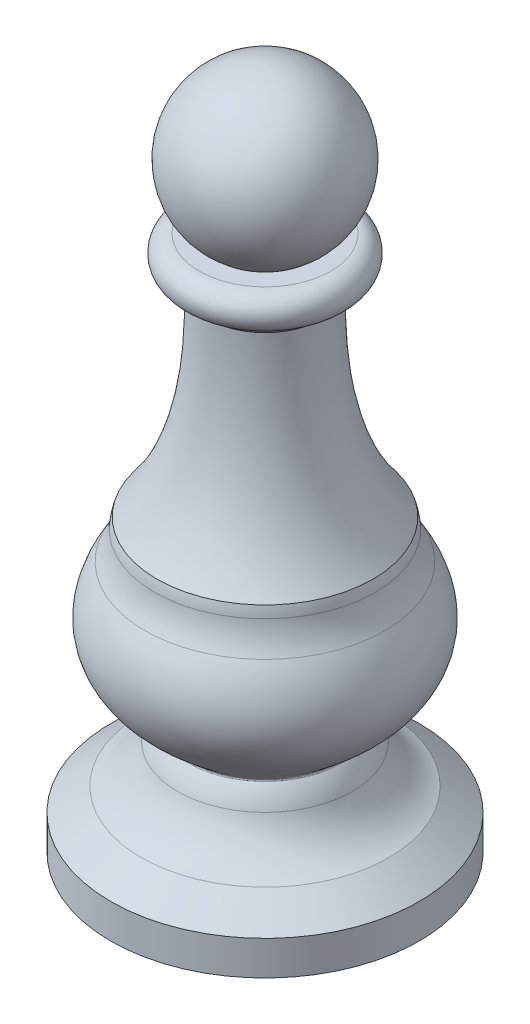
SolidWorks part; units mm, degrees
ref_plane "Front Plane" through (0, 0, 0) normal (0, 0, 1) x (1, 0, 0)
ref_plane "Top Plane" through (0, 0, 0) normal (0, 1, 0) x (1, 0, 0)
ref_plane "Right Plane" through (0, 0, 0) normal (1, 0, 0) x (0, 0, -1)
sketch "Sketch1" plane through (0, 0, 0) normal (0, 1, 0) x (1, 0, 0)
  line L1 (-32.5, -32.5) -> (32.5, -32.5) construction
  line L2 (-32.5, -32.5) -> (-32.5, 32.5) construction
  line L3 (-32.5, 32.5) -> (32.5, 32.5) construction
  line L4 (32.5, -32.5) -> (32.5, 32.5) construction
  line L5 (-32.5, -32.5) -> (32.5, 32.5) construction
  line L6 (-32.5, 32.5) -> (32.5, -32.5) construction
  circle A0 centre (0, 0) radius 7.8333
  point P0 (0, 0)
  dimension "D2" = 15.6667
  dimension "D1" = 65
extrude "Boss-Extrude1" add sketch "Sketch1" along normal blind 5 contours A0
sketch "Sketch2" plane through (0, 0, 0) normal (0, 0, 1) x (1, 0, 0)
  line L0 (0, 0) -> (0, 20.8703) construction
  line L2 (7.8333, 5) -> (-7.8333, 5) construction
  line L3 (6.8333, 5) -> (0, 5)
  line L4 (0, 20.8703) -> (0, 5)
  line L6 (7.6047, 20.8703) -> (0, 20.8703)
  line L7 (-7.8333, 0) -> (7.8333, 0) construction
  spline S0 degree 3 poles (6.8333, 5) (5.1129, 5.4872) (18.2724, 9.971) (7.6372, 20.4604) (7.6047, 20.8703) knots 0 0 0 0 0.888569 0.92213 0.92213 0.92213 0.92213
  point P6 (10.5698, 8.9299)
  dimension "D1" = 20.8703
  dimension "D2" = 1
revolve "Revolve1" add sketch "Sketch2" angle 360 about L0 region at (5.1972, 13.0016, 0)
fillet "Fillet3" radius 5 1 edges at (0, 5, 7.8333)
ref_plane "Plane1" through (0, 27.8703, 0) normal (0, 1, 0) x (1, 0, 0)
sketch "Sketch5" plane through (0, 27.8703, 0) normal (0, 1, 0) x (1, 0, 0)
  circle A0 centre (0, 0) radius 5
  dimension "D1" = 10
ref_plane "Plane2" through (0, 19.8703, 0) normal (0, 1, 0) x (1, 0, 0)
sketch "Sketch6" plane through (0, 19.8703, 0) normal (0, 1, 0) x (1, 0, 0)
  circle A0 centre (0, 0) radius 9.6047
  circle A1 centre (0, 0) radius 7.6047 construction
  dimension "D1" = 2
loft "Loft1" add profiles "Sketch6", "Sketch5" connector at (9.0946, 19.8703, 3.0883) connector at (4.6993, 27.8703, 1.7077)
sketch "Sketch8" plane through (0, 27.8703, 0) normal (0, 1, 0) x (1, 0, 0)
  circle A1 centre (0, 0) radius 5
  circle A2 centre (0, 0) radius 5
  dimension "D1" = 0
extrude "Boss-Extrude2" add sketch "Sketch8" along normal blind 10
sketch "Sketch9" plane through (0, 37.8703, 0) normal (0, 1, 0) x (1, 0, 0)
  circle A1 centre (0, 0) radius 5
  circle A2 centre (0, 0) radius 5
  dimension "D1" = 0
extrude "Boss-Extrude3" add sketch "Sketch9" along normal blind 1 draft 37 draft outward yes
sketch "Sketch10" plane through (0, 0, 0) normal (1, 0, 0) x (0, 0, -1)
  line L0 (0, 37.8703) -> (0, 19.8703) construction
  line L1 (-5, 37.8703) -> (5, 37.8703) construction
  line L2 (-8.2222, 19.8703) -> (8.2222, 19.8703) construction
  line L3 (-9.6047, 19.8703) -> (9.6047, 19.8703) construction
  line L4 (0, 19.8703) -> (9.6047, 19.8703)
  line L5 (0, 37.8703) -> (5, 37.8703)
  line L6 (0, 37.8703) -> (0, 19.8703)
  spline S0 degree 2 poles (5, 37.8703) (7.1218, 28.575) (9.6047, 19.8703) knots 0 0 0 0.621696 0.621696 0.621696
revolve "Revolve2" add sketch "Sketch10" angle 360 about L0
sketch "Sketch11" plane through (0, 0, 0) normal (1, 0, 0) x (0, 0, -1)
  line L0 (0, 37.8703) -> (0, 52.3767) construction
  line L1 (-5, 37.8703) -> (5, 37.8703) construction
  line L2 (5.7536, 41.8703) -> (0, 41.8703)
  line L3 (5.7536, 38.8703) -> (0, 38.8703)
  line L4 (5.7536, 38.8703) -> (-5.7536, 38.8703) construction
  line L5 (0, 38.8703) -> (0, 41.8703)
  arc A0 (5.7536, 38.8703) -> (5.7536, 41.8703) centre (5.7536, 40.3703) ccw
  dimension "D1" = 1.5
revolve "Revolve3" add sketch "Sketch11" angle 360 about L0
sketch "Sketch12" plane through (0, 0, 0) normal (1, 0, 0) x (0, 0, -1)
  line L0 (0, 41.8703) -> (0, 54.4959) construction
  line L1 (5.7536, 41.8703) -> (-5.7536, 41.8703) construction
  line L2 (0, 41.8703) -> (0, 0) construction
  line L3 (0, 54.4959) -> (0, 40.4959)
  arc A0 (0, 54.4959) -> (0, 40.4959) centre (0, 47.4959) cw
  dimension "D1" = 14
revolve "Revolve4" add sketch "Sketch12" angle 360 about L3
fillet "Fillet6" radius 6 1 edges at (8.2222, 19.8703, 0)
sketch "Sketch13" plane through (0, 0, 0) normal (0, -1, 0) x (1, 0, 0)
  circle A0 centre (0, 0) radius 10.8333
  circle A1 centre (0, 0) radius 7.8333 construction
  dimension "D1" = 3
extrude "Boss-Extrude4" add sketch "Sketch13" along normal blind 2 draft 53 draft outward yes
fillet "Fillet7" radius 6 1 edges at (0, 0, 7.8333)
fillet "Fillet8" radius 6 1 edges at (-9.6047, 19.8703, 0)
sketch "Sketch14" plane through (0, 0, 0) normal (0, 0, 1) x (1, 0, 0)
  line L0 (0, 0) -> (0, 38.8703) construction
  line L1 (-5.7536, 38.8703) -> (5.7536, 38.8703) construction
  line L2 (5, 37.8703) -> (-5, 37.8703) construction
  line L3 (0, 37.8703) -> (-5, 37.8703)
  spline S0 degree 2 poles (933.4459, 402.8116) (-416.3017, -869.4145) (170.1772, 1024.1248) knots -27.459131 -27.459131 -27.459131 18.062843 18.062843 18.062843 only from (9.4542, 20.3997) to (5, 37.8703) construction
  spline S1 degree 2 poles (9.4542, 20.3997) (7.0573, 28.8574) (5, 37.8703) knots 0.018885 0.018885 0.018885 0.621696 0.621696 0.621696
  spline S2 degree 2 poles (5, 37.8703) (4.6708, 26.305) (9.4542, 20.3997) knots 0 0 0 0.759883 0.759883 0.759883
revolve "Cut-Revolve1" cut sketch "Sketch14" angle 360 about L0
fillet "Fillet9" radius 6 1 edges at (6.8333, 5, 0)
sketch "Sketch15" plane through (0, -2, 0) normal (0, -1, 0) x (1, 0, 0)
  circle A1 centre (0, 0) radius 13.4874
  circle A2 centre (0, 0) radius 13.4874
  dimension "D1" = 0
extrude "Boss-Extrude5" add sketch "Sketch15" along normal blind 3
